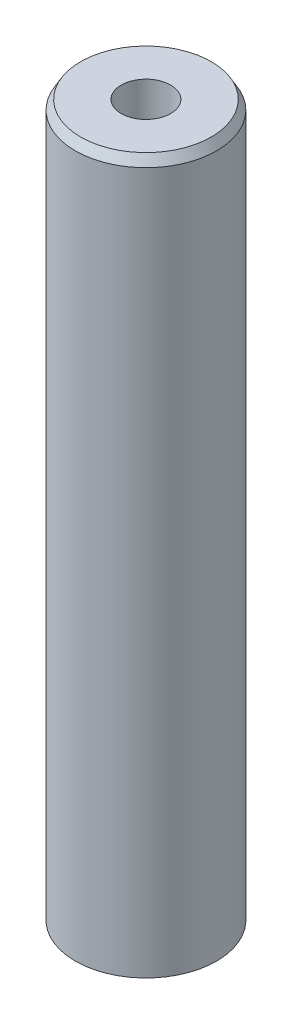
SolidWorks part; units mm, degrees
ref_plane "Front Plane" through (0, 0, 0) normal (0, 0, 1) x (1, 0, 0)
ref_plane "Top Plane" through (0, 0, 0) normal (0, 1, 0) x (1, 0, 0)
ref_plane "Right Plane" through (0, 0, 0) normal (1, 0, 0) x (0, 0, -1)
sketch "Sketch1" plane through (0, 0, 0) normal (0, 1, 0) x (1, 0, 0)
  circle A0 centre (0, 0) radius 27.5
  dimension "SHAFT_OD" = 55
extrude "Boss-Extrude1" add sketch "Sketch1" along normal blind 278.7622
sketch "Sketch2" plane through (0, 0, 0) normal (0, 1, 0) x (1, 0, 0)
  circle A0 centre (0, 0) radius 9.6226
  dimension "BORE_D" = 19.2453
extrude "Cut-Extrude1" cut sketch "Sketch2" along normal through all
chamfer "Chamfer1" distance 3.6143 angle 30 2 edges at (0, 278.7622, 27.5) (0, 0, 27.5) first distance on face at (0, 278.7622, 27.5) first distance on face at (0, 0, 9.6226)
